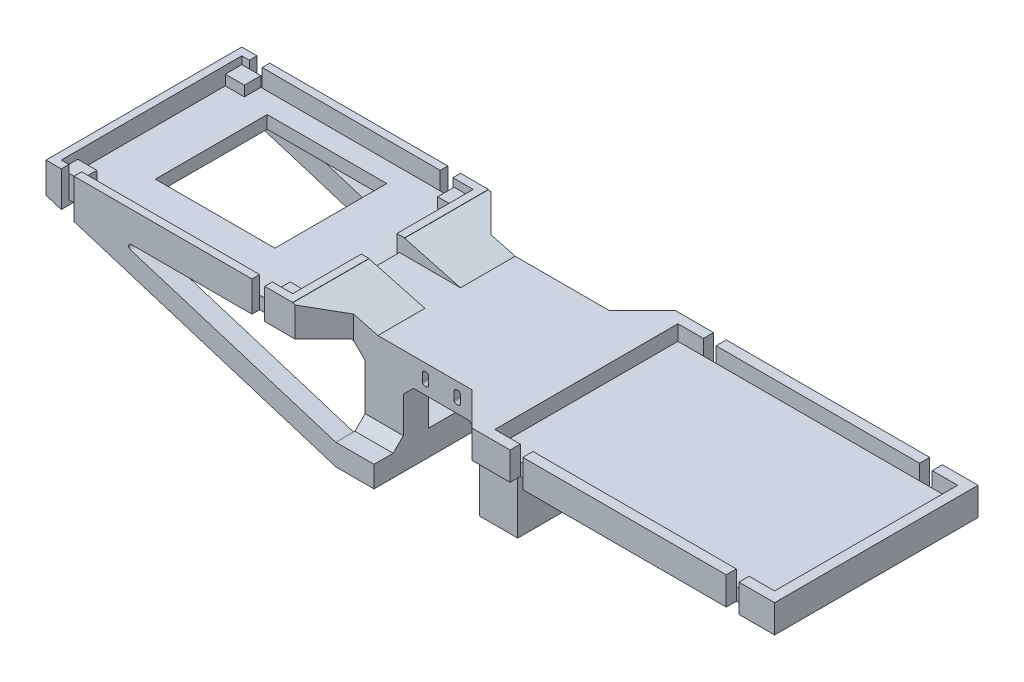
SolidWorks part; units mm, degrees
ref_plane "Front Plane" through (0, 0, 0) normal (0, 0, 1) x (1, 0, 0)
ref_plane "Top Plane" through (0, 0, 0) normal (0, 1, 0) x (1, 0, 0)
ref_plane "Right Plane" through (0, 0, 0) normal (1, 0, 0) x (0, 0, -1)
sketch "Sketch2" plane through (0, 0, 0) normal (1, 0, 0) x (0, 0, -1)
  line L1 (-17, -20.5) -> (17, -20.5)
  line L2 (-17, -20.5) -> (-17, 0)
  line L3 (-17, 0) -> (17, 0)
  line L4 (17, -20.5) -> (17, 0)
  line L5 (27, 11) -> (-27, 11)
  line L6 (27, 11) -> (27, -30.5)
  line L7 (27, -30.5) -> (-27, -30.5)
  line L8 (-27, 11) -> (-27, -30.5)
  line L9 (27, 11) -> (-27, -30.5) construction
  line L10 (27, -30.5) -> (-27, 11) construction
  point P4 (0, 0)
  point P6 (0, -9.75)
  point P11 (0, 0)
  point P13 (0, 0)
  dimension "D1" = 34
  dimension "D2" = 20.5
  dimension "D3" = 11
  dimension "D4" = 10
  dimension "D5" = 10
extrude "Boss-Extrude1" add sketch "Sketch2" against normal blind 80
sketch "Sketch4" plane through (0, 0, 27) normal (0, 0, 1) x (1, 0, 0)
  line L0 (-80, -30.5) -> (0, -30.5) construction
  line L1 (-45, -30.5) -> (-15, -30.5)
  line L2 (-45, -30.5) -> (-45, 0)
  line L3 (-45, 0) -> (-15, 0)
  line L4 (-15, -30.5) -> (-15, 0)
  line L5 (0, 11) -> (0, -30.5) construction
  line L8 (-80, -30.5) -> (-60, -30.5)
  line L9 (-80, -30.5) -> (-80, 0)
  line L10 (-80, 0) -> (-60, 0)
  line L11 (-60, -30.5) -> (-60, 0)
  dimension "D1" = 15
  dimension "D2" = 30
  dimension "D3" = 20
extrude "Cut-Extrude2" cut sketch "Sketch4" against normal up to surface (54 mm away) up to face at (-40, -9.75, -27)
ref_plane "Plane1" through (0, 5, 0) normal (0, 1, 0) x (1, 0, 0)
sketch "Sketch7" plane through (0, 5, 0) normal (0, 1, 0) x (1, 0, 0)
  line L0 (-80, 27) -> (-80, -27) construction
  line L1 (-80, 35.5) -> (-171, 35.5)
  line L2 (-80, 35.5) -> (-80, -35.5)
  line L3 (-80, -35.5) -> (-171, -35.5)
  line L4 (-171, 35.5) -> (-171, -35.5)
  point P6 (-80, 0)
  dimension "D1" = 71
  dimension "D2" = 91
extrude "Boss-Extrude2" add sketch "Sketch7" along normal blind 5
sketch "Sketch8" plane through (0, 11, 0) normal (0, 1, 0) x (1, 0, 0)
  line L0 (-80, 35.5) -> (-171, 35.5) construction
  line L1 (-153, -16.5) -> (-106, -16.5)
  line L2 (-153, -16.5) -> (-153, 27.5)
  line L3 (-153, 27.5) -> (-106, 27.5)
  line L4 (-106, -16.5) -> (-106, 27.5)
  line L5 (-153, -16.5) -> (-106, 27.5) construction
  line L6 (-153, 27.5) -> (-106, -16.5) construction
  line L7 (-171, 35.5) -> (-171, -35.5) construction
  line L8 (-171, -35.5) -> (-80, -35.5) construction
  line L9 (-80, -35.5) -> (-80, -27) construction
  point P0 (-129.5, 5.5)
  dimension "D1" = 19
  dimension "D2" = 18
  dimension "D3" = 8
  dimension "D4" = 26
extrude "Cut-Extrude3" cut sketch "Sketch8" against normal up to surface (6 mm away) up to face at (-110.3333, 5, 0)
sketch "Sketch10" plane through (0, 5, 0) normal (0, -1, 0) x (1, 0, 0)
  line L1 (-174, 38.5) -> (-77, 38.5)
  line L2 (-174, 38.5) -> (-174, -38.5)
  line L3 (-174, -38.5) -> (-77, -38.5)
  line L4 (-77, 38.5) -> (-77, -38.5)
  line L5 (-174, 38.5) -> (-77, -38.5) construction
  line L6 (-174, -38.5) -> (-77, 38.5) construction
  line L8 (-171, 35.5) -> (-80, 35.5) construction
  line L9 (-171, -35.5) -> (-171, 35.5) construction
  line L10 (-80, -35.5) -> (-171, -35.5) construction
  line L17 (-80, 27) -> (-80, 35.5)
  line L18 (-80, -27) -> (-80, 27)
  line L19 (-80, -35.5) -> (-80, -27)
  line L20 (-171, -35.5) -> (-80, -35.5)
  line L21 (-171, 35.5) -> (-171, -35.5)
  line L22 (-80, 35.5) -> (-171, 35.5)
  line L23 (-80, 27) -> (-80, 35.5)
  line L24 (-80, -27) -> (-80, 27)
  line L25 (-80, -35.5) -> (-80, -27)
  line L26 (-171, -35.5) -> (-80, -35.5)
  line L27 (-171, 35.5) -> (-171, -35.5)
  line L28 (-80, 35.5) -> (-171, 35.5)
  point P0 (-125.5, 0)
  point P5 (0, 0)
  point P6 (0, 0)
  point P8 (0, 0)
  point P11 (-125.5, 35.5)
  dimension "D1" = 3
  dimension "D2" = 3
  dimension "D3" = 0
extrude "Boss-Extrude3" add sketch "Sketch10" against normal blind 12
sketch "Sketch11" plane through (0, 10, 0) normal (0, 1, 0) x (1, 0, 0)
  line L0 (-171, 35.5) -> (-80, 35.5) construction
  line L1 (-87.5, -29) -> (-163.5, -29) construction
  line L2 (-87.5, -29) -> (-87.5, 29) construction
  line L3 (-87.5, 29) -> (-163.5, 29) construction
  line L4 (-163.5, -29) -> (-163.5, 29) construction
  line L5 (-87.5, -29) -> (-163.5, 29) construction
  line L6 (-87.5, 29) -> (-163.5, -29) construction
  line L8 (-171, -35.5) -> (-163.5, -35.5)
  line L9 (-171, -35.5) -> (-171, -29)
  line L10 (-171, -29) -> (-163.5, -29)
  line L11 (-163.5, -35.5) -> (-163.5, -29)
  line L12 (-80, -35.5) -> (-87.5, -35.5)
  line L13 (-80, -35.5) -> (-80, -29)
  line L14 (-80, -29) -> (-87.5, -29)
  line L15 (-87.5, -35.5) -> (-87.5, -29)
  line L16 (-80, 35.5) -> (-87.5, 35.5)
  line L17 (-80, 35.5) -> (-80, 29)
  line L18 (-80, 29) -> (-87.5, 29)
  line L19 (-87.5, 35.5) -> (-87.5, 29)
  line L20 (-171, 35.5) -> (-163.5, 35.5)
  line L21 (-171, 35.5) -> (-171, 29)
  line L22 (-171, 29) -> (-163.5, 29)
  line L23 (-163.5, 35.5) -> (-163.5, 29)
  point P0 (-125.5, 0)
  point P7 (-125.5, 35.5)
  point P8 (-125.5, 29)
  dimension "D1" = 76
  dimension "D2" = 58
extrude "Boss-Extrude4" add sketch "Sketch11" along normal blind 4
sketch "Sketch12" plane through (0, 17, 0) normal (0, 1, 0) x (1, 0, 0)
  line L0 (-80, 35.5) -> (-80, -35.5) construction
  line L1 (-80, 5.5) -> (-77, 5.5)
  line L2 (-80, 5.5) -> (-80, -8.5)
  line L3 (-80, -8.5) -> (-77, -8.5)
  line L4 (-77, 5.5) -> (-77, -8.5)
  line L5 (-77, 38.5) -> (-77, -38.5) construction
  line L6 (-80, -35.5) -> (-171, -35.5) construction
  line L7 (-80, 35.5) -> (-87.5, 35.5) construction
  point P8 (-80, -1.5)
  dimension "D1" = 27
  dimension "D2" = 30
extrude "Cut-Extrude5" cut sketch "Sketch12" against normal up to surface (6 mm away) up to face at (-38.5, 11, 0)
sketch "Sketch13" plane through (0, 0, 27) normal (0, 0, 1) x (1, 0, 0)
  line L0 (-15, 0) -> (-45, 0) construction
  line L1 (-25, 8) -> (-22.5, 8)
  line L2 (-25, 8) -> (-25, 3)
  line L3 (-25, 3) -> (-22.5, 3)
  line L4 (-22.5, 8) -> (-22.5, 3)
  point P6 (-30, 0)
  point P8 (-25, 5.5)
  dimension "D1" = 3
  dimension "D2" = 5
  dimension "D3" = 2.5
  dimension "D4" = 5
extrude "Cut-Extrude6" cut sketch "Sketch13" against normal up to surface (54 mm away) up to face at (-46.1667, -7.5, -27)
sketch "Sketch15" plane through (0, 0, 38.5) normal (0, 0, 1) x (1, 0, 0)
  line L0 (-174, 5) -> (-60, -30.5)
  line L2 (-60, -30.5) -> (-60, 0) construction
  line L3 (-60, -22.1211) -> (-147.0931, 5)
  line L4 (-77, 5) -> (-174, 5) construction
  line L5 (-147.0931, 5) -> (-174, 5)
  line L6 (-45, 0) -> (-45, -30.5) construction
  line L7 (-60, -30.5) -> (-45, -30.5)
  line L9 (-60, -22.1211) -> (-45, -22.1211)
  line L10 (-45, -30.5) -> (-45, -22.1211)
  dimension "D1" = 8
extrude "Boss-Extrude5" add sketch "Sketch15" against normal up to surface (77 mm away) up to face at (-125.5, 11, -38.5)
sketch "Sketch18" plane through (0, -30.5, 0) normal (0, -1, 0) x (1, 0, 0)
  line L0 (-60, -38.5) -> (-60, 38.5) construction
  line L1 (-60, 31.5) -> (-174, 31.5)
  line L2 (-60, 31.5) -> (-60, -31.5)
  line L3 (-60, -31.5) -> (-174, -31.5)
  line L4 (-174, 31.5) -> (-174, -31.5)
  line L6 (-153, -27.5) -> (-106, -27.5) construction
  line L7 (-153, -27.5) -> (-106, -27.5) construction
  line L8 (-174, 38.5) -> (-174, -38.5) construction
  point P6 (-60, 0)
  dimension "D1" = 4
extrude "Cut-Extrude8" cut sketch "Sketch18" against normal up to surface (35.5 mm away) up to face at (-105.6977, 5, -1.8333)
chamfer "Chamfer2" distance 5 angle 45 1 edges at (-60, 5, 0)
fillet "Fillet1" radius 1 4 edges at (-60, -22.1211, 35) (-60, -22.1211, -35) (-147.0931, 5, -35) (-147.0931, 5, 35)
chamfer "Chamfer3" distance 4 angle 45 6 edges at (-52.5, -22.1211, 27) (-52.5, -22.1211, -27) (-45, 0, -22) (-45, 0, 22) (-15, 0, 22) (-15, 0, -22)
chamfer "Chamfer4" distance 12.5 angle 45 2 edges at (-77, 8, 27) (-77, 8, -27)
fillet "Fillet2" radius 1 4 edges at (-22.5, 3, 0) (-22.5, 8, 0) (-25, 3, 0) (-25, 8, 0)
chamfer "Chamfer5" distance 1 angle 45 1 edges at (-80, 11, 1.5)
ref_plane "Plane2" through (-30, 0, 0) normal (1, 0, 0) x (0, 0, -1)
mirror "Mirror1" about plane through (-30, 0, 0) normal (1, 0, 0) of "Fillet2", "Cut-Extrude6"
sketch "Sketch19" plane through (0, 5, 0) normal (0, 1, 0) x (1, 0, 0)
  line L1 (0, 36) -> (110, 36)
  line L2 (0, 36) -> (0, -36)
  line L3 (0, -36) -> (110, -36)
  line L4 (110, 36) -> (110, -36)
  point P4 (0, 0)
  dimension "D1" = 110
  dimension "D2" = 72
extrude "Boss-Extrude6" add sketch "Sketch19" along normal blind 5 from surface starting at face at (-30, 0, 0)
sketch "Sketch21" plane through (0, 5, 0) normal (0, 1, 0) x (1, 0, 0)
  line L0 (110, 36) -> (0, 36) construction
  line L1 (114, -40) -> (-4, -40)
  line L2 (114, -40) -> (114, 40)
  line L3 (114, 40) -> (-4, 40)
  line L4 (-4, -40) -> (-4, 40)
  line L5 (114, -40) -> (-4, 40) construction
  line L6 (114, 40) -> (-4, -40) construction
  line L7 (0, 36) -> (0, 27) construction
  line L14 (0, 36) -> (0, 27)
  line L15 (0, 27) -> (0, -27)
  line L16 (0, -27) -> (0, -36)
  line L17 (0, -36) -> (110, -36)
  line L18 (110, -36) -> (110, 36)
  line L19 (110, 36) -> (0, 36)
  line L20 (0, 36) -> (0, 27)
  line L21 (0, 27) -> (0, -27)
  line L22 (0, -27) -> (0, -36)
  line L23 (0, -36) -> (110, -36)
  line L24 (110, -36) -> (110, 36)
  line L25 (110, 36) -> (0, 36)
  point P0 (55, 0)
  point P5 (0, 0)
  point P8 (55, 36)
  dimension "D1" = 4
  dimension "D2" = 4
  dimension "D3" = 0
extrude "Boss-Extrude7" add sketch "Sketch21" along normal up to surface (6 mm away) from surface up to face at (-62.25, 11, 0.5) starting at face at (-7.7778, 0, 0)
chamfer "Chamfer7" distance 14 angle 45 2 edges at (-4, 5.5, -27) (-4, 5.5, 27)
sketch "Sketch22" plane through (0, 11, 0) normal (0, 1, 0) x (1, 0, 0)
  line L0 (110, 36) -> (0, 36) construction
  line L1 (100, 36) -> (95, 36)
  line L2 (100, 36) -> (100, 40)
  line L3 (100, 40) -> (95, 40)
  line L4 (95, 36) -> (95, 40)
  line L5 (114, 40) -> (-5, 40) construction
  line L6 (0, -36) -> (110, -36) construction
  line L7 (95, -36) -> (100, -36)
  line L8 (95, -36) -> (95, -40)
  line L9 (95, -40) -> (100, -40)
  line L10 (100, -36) -> (100, -40)
  line L11 (-5, -40) -> (114, -40) construction
  line L12 (0, -36) -> (110, -36) construction
  line L13 (10, -36) -> (15, -36)
  line L14 (10, -36) -> (10, -40)
  line L15 (10, -40) -> (15, -40)
  line L16 (15, -36) -> (15, -40)
  line L17 (110, 36) -> (0, 36) construction
  line L18 (10, 40) -> (15, 40)
  line L19 (10, 40) -> (10, 36)
  line L20 (10, 36) -> (15, 36)
  line L21 (15, 40) -> (15, 36)
  line L22 (110, -36) -> (110, 36) construction
  line L23 (0, 36) -> (0, -36) construction
  point P28 (23.2864, -40)
  dimension "D1" = 5
  dimension "D2" = 10
  dimension "D3" = 10
extrude "Cut-Extrude9" cut sketch "Sketch22" against normal up to surface (11 mm away) up to face at (-8.9, 0, 0)
sketch "Sketch23" plane through (0, 17, 0) normal (0, 1, 0) x (1, 0, 0)
  line L0 (-174, 38.5) -> (-77, 38.5) construction
  line L1 (-168, 38.5) -> (-163, 38.5)
  line L2 (-168, 38.5) -> (-168, 35.5)
  line L3 (-168, 35.5) -> (-163, 35.5)
  line L4 (-163, 38.5) -> (-163, 35.5)
  line L5 (-171, 35.5) -> (-80, 35.5) construction
  line L6 (-80, 35.5) -> (-87.5, 35.5) construction
  line L7 (-93, 38.5) -> (-88, 38.5)
  line L8 (-93, 38.5) -> (-93, 35.5)
  line L9 (-93, 35.5) -> (-88, 35.5)
  line L10 (-88, 38.5) -> (-88, 35.5)
  line L11 (-77, -38.5) -> (-174, -38.5) construction
  line L12 (-88, -38.5) -> (-93, -38.5)
  line L13 (-88, -38.5) -> (-88, -35.5)
  line L14 (-88, -35.5) -> (-93, -35.5)
  line L15 (-93, -38.5) -> (-93, -35.5)
  line L16 (-163.5, -35.5) -> (-87.5, -35.5) construction
  line L18 (-163, -35.5) -> (-168, -35.5)
  line L19 (-163, -35.5) -> (-163, -38.5)
  line L20 (-163, -38.5) -> (-168, -38.5)
  line L21 (-168, -35.5) -> (-168, -38.5)
  line L22 (-171, 35.5) -> (-171, 29) construction
  line L23 (-80, 35.5) -> (-80, 5.5) construction
  dimension "D1" = 5
  dimension "D2" = 8
  dimension "D3" = 8
extrude "Cut-Extrude10" cut sketch "Sketch23" against normal up to surface (12 mm away) up to face at (-119.2074, 5, 0)
sketch "Sketch24" plane through (0, 5, 0) normal (0, -1, 0) x (1, 0, 0)
  line L0 (-168, 38.5) -> (-163, 38.5) construction
  line L1 (-168, 38.5) -> (-163, 38.5)
  line L2 (-168, 38.5) -> (-168, -38.5)
  line L3 (-168, -38.5) -> (-163, -38.5)
  line L4 (-163, -38.5) -> (-163, 38.5)
extrude "Cut-Extrude11" cut sketch "Sketch24" along normal up to surface (3.4254 mm away) up to face at (-117, -12.75, 35)
chamfer "Chamfer8" distance 22 angle 15 2 edges at (-77, 11, -22) (-77, 11, 23.5) first distance on face at (-37.65, 11, 0.3)
